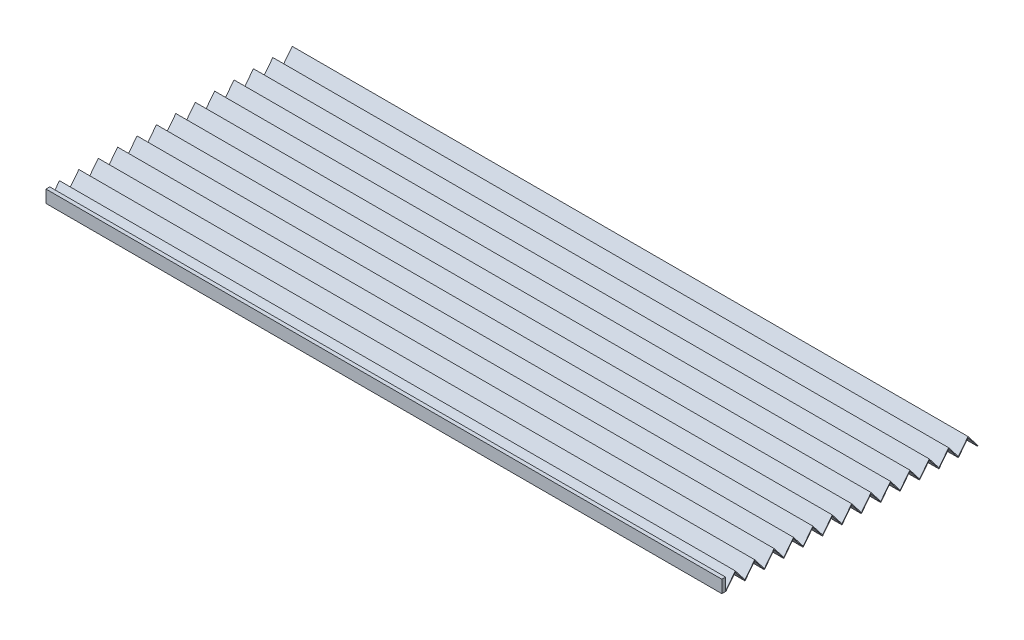
SolidWorks part; units mm, degrees
ref_plane "Front Plane" through (0, 0, 0) normal (0, 0, 1) x (1, 0, 0)
ref_plane "Top Plane" through (0, 0, 0) normal (0, 1, 0) x (1, 0, 0)
ref_plane "Right Plane" through (0, 0, 0) normal (1, 0, 0) x (0, 0, -1)
sketch "Sketch2" plane through (0, 0, 0) normal (0, 0, 1) x (1, 0, 0)
  line L1 (-270, 10) -> (270, 10)
  line L2 (-270, 10) -> (-270, 0)
  line L3 (-270, 0) -> (270, 0)
  line L4 (270, 10) -> (270, 0)
  point P4 (0, 0)
  dimension "D1" = 10
  dimension "D2" = 540
extrude "Boss-Extrude1" add sketch "Sketch2" along normal blind 3
sketch "Sketch3" plane through (270, 0, 0) normal (1, 0, 0) x (0, 0, -1)
  line L0 (0, 10) -> (201.4696, 10) construction
  line L1 (0, 0) -> (201.4696, 0) construction
  line L2 (201.4696, 10) -> (201.4696, 0) construction
  line L3 (0, 0) -> (7.7488, 10)
  line L4 (7.7488, 10) -> (15.4977, 0)
  line L5 (15.4977, 0) -> (23.2465, 10)
  line L6 (23.2465, 10) -> (30.9953, 0)
  line L7 (30.9953, 0) -> (38.7442, 10)
  line L8 (38.7442, 10) -> (46.493, 0)
  line L9 (46.493, 0) -> (54.2418, 10)
  line L10 (54.2418, 10) -> (61.9907, 0)
  line L11 (61.9907, 0) -> (69.7395, 10)
  line L12 (69.7395, 10) -> (77.4883, 0)
  line L13 (77.4883, 0) -> (85.2371, 10)
  line L14 (85.2371, 10) -> (92.986, 0)
  line L15 (92.986, 0) -> (100.7348, 10)
  line L16 (100.7348, 10) -> (108.4836, 0)
  line L17 (108.4836, 0) -> (116.2325, 10)
  line L18 (116.2325, 10) -> (123.9813, 0)
  line L20 (123.9813, 0) -> (131.7301, 10)
  line L21 (131.7301, 10) -> (139.479, 0)
  line L22 (139.479, 0) -> (147.2278, 10)
  line L23 (147.2278, 10) -> (154.9766, 0)
  line L24 (154.9766, 0) -> (162.7255, 10)
  line L25 (162.7255, 10) -> (170.4743, 0)
  line L26 (170.4743, 0) -> (178.2231, 10)
  line L27 (178.2231, 10) -> (185.972, 0)
  line L28 (185.972, 0) -> (193.7208, 10)
  line L29 (193.7208, 10) -> (201.4696, 0)
  line L30 (201.4696, 10) -> (201.4696, 0) construction
extrude "Extrude-Thin1" add sketch "Sketch3" against normal through all thin thin type mid plane wall 0.5
